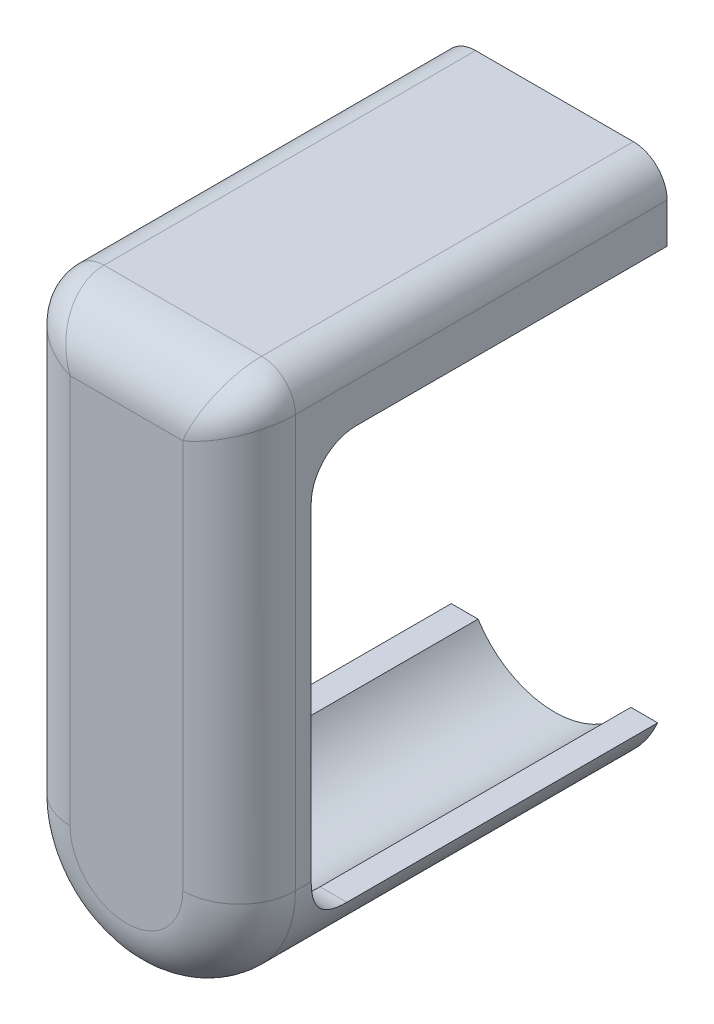
SolidWorks part; units mm, degrees
material "Cast Alloy Steel"
ref_plane "Front Plane" through (0, 0, 0) normal (0, 0, 1) x (1, 0, 0)
ref_plane "Top Plane" through (0, 0, 0) normal (0, 1, 0) x (1, 0, 0)
ref_plane "Right Plane" through (0, 0, 0) normal (1, 0, 0) x (0, 0, -1)
sketch "Sketch1" plane through (0, 0, 0) normal (0, 0, 1) x (1, 0, 0)
  line L0 (-5, 9.9) -> (5, -9.9) construction
  line L2 (-5, -9.9) -> (-5, 9.9)
  line L3 (-5, 9.9) -> (5, 9.9)
  line L4 (5, -9.9) -> (5, 9.9)
  line L5 (5, 9.9) -> (-5, -9.9) construction
  arc A0 (-5, -9.9) -> (5, -9.9) centre (0, -9.9) ccw
  point P0 (0, 0)
  point P4 (0, 0)
  point P8 (0, -14.9)
  point P9 (0, 9.9)
  dimension "D1" = 24.8
  dimension "D2" = 10
extrude "Boss-Extrude1" add sketch "Sketch1" along normal blind 19
sketch "Sketch2" plane through (0, 0, 0) normal (0, 0, 1) x (1, 0, 0)
  line L0 (4, 5.0203) -> (-4, -9.7797) construction
  line L2 (-4, -9.7797) -> (-4, 5.0203)
  line L4 (4, -9.7797) -> (4, 5.0203)
  line L5 (-4, 5.0203) -> (4, -9.7797) construction
  line L6 (0, -1000) -> (0, 49000) construction
  arc A0 (-4, -9.7797) -> (4, -9.7797) centre (0, -9.7797) ccw
  arc A1 (4, 5.0203) -> (-4, 5.0203) centre (0, 5.0203) ccw
  point P0 (0, 0)
  point P5 (0, -2.3797)
extrude "Cut-Extrude2" cut sketch "Sketch2" along normal blind 18
fillet "Fillet2" radius 2.5 4 edges at (-5, 0, 19) (0, -14.9, 19) (0, 9.9, 19) (5, 0, 19)
sketch "Sketch4" plane through (0, 0, 0) normal (1, 0, 0) x (0, 0, -1)
  line L0 (0, -14.9) -> (0, -9.9) construction
  line L1 (0, -11.9) -> (-13.8, -11.9)
  line L2 (0, -11.9) -> (0, 6.629)
  line L3 (0, 6.629) -> (-13.8, 6.629)
  line L4 (-15.8, -9.9) -> (-15.8, 4.629)
  line L5 (-16.5, -14.9) -> (0, -14.9) construction
  line L6 (-16.5, 9.9) -> (0, 9.9) construction
  line L7 (-19, -9.9) -> (-19, 7.4) construction
  arc A0 (-13.8, -11.9) -> (-15.8, -9.9) centre (-13.8, -9.9) cw
  arc A1 (-13.8, 6.629) -> (-15.8, 4.629) centre (-13.8, 4.629) ccw
  dimension "D4" = 2
  dimension "D1" = 3
  dimension "D2" = 3.271
  dimension "D3" = 3.2
extrude "Cut-Extrude3" cut sketch "Sketch4" against normal through all and the other way through all
fillet "Fillet3" radius 1.5 4 edges at (4.2678, 9.1678, 18.2678) (-4.2678, 9.1678, 18.2678) (5, 9.9, 8.25) (-5, 9.9, 8.25)
sketch "Sketch5" plane through (0, 0, 18) normal (0, 0, -1) x (-1, 0, 0)
  line L0 (-1000, 0) -> (49000, 0) construction
  line L1 (-4, 6.3) -> (-1.5, 6.3)
  line L2 (-4, 6.3) -> (-4, -3.7)
  line L3 (-4, -3.7) -> (-1.5, -3.7)
  line L4 (-1.5, 6.3) -> (-1.5, -3.7)
  line L6 (-4, -9.7797) -> (-4, 5.0203) construction
  dimension "D1" = 6.3
  dimension "D2" = 10
extrude "Boss-Extrude2" add sketch "Sketch5" along normal blind 2.5
sketch "Sketch6" plane through (0, 6.3, 0) normal (0, 1, 0) x (1, 0, 0)
  line L5 (-997, -16.75) -> (49003, -16.75) construction
  line L6 (4, -15.8) -> (4, -18) construction
  circle A0 centre (3, -16.75) radius 1
  point P12 (4, -16.75)
  dimension "D1" = 2
extrude "Cut-Extrude4" cut sketch "Sketch6" against normal blind 11
